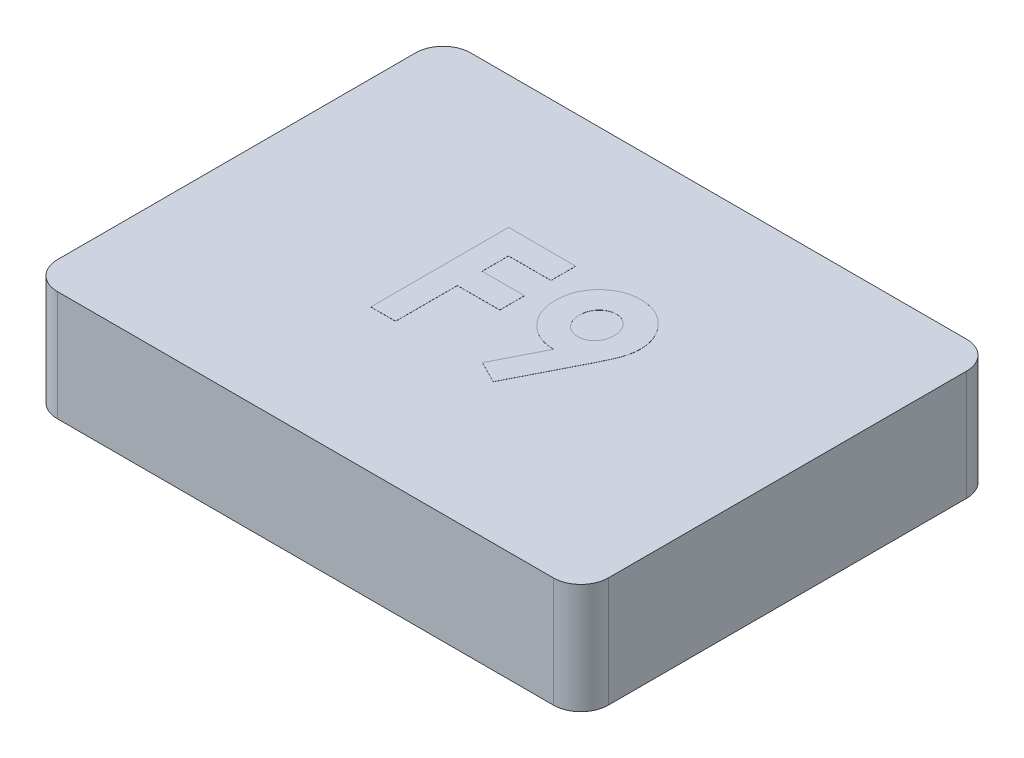
SolidWorks part; units mm, degrees
ref_plane "Front Plane" through (0, 0, 0) normal (0, 0, 1) x (1, 0, 0)
ref_plane "Top Plane" through (0, 0, 0) normal (0, 1, 0) x (1, 0, 0)
ref_plane "Right Plane" through (0, 0, 0) normal (1, 0, 0) x (0, 0, -1)
sketch "Sketch1" plane through (0, 0, 0) normal (0, 1, 0) x (1, 0, 0)
  line L0 (0, 0) -> (12.7, 0)
  line L1 (12.7, 0) -> (12.7, 9.525)
  line L2 (12.7, 9.525) -> (0, 9.525)
  line L3 (0, 9.525) -> (0, 0)
  dimension "D1" = 12.7
  dimension "D2" = 9.525
extrude "Boss-Extrude1" add sketch "Sketch1" along normal blind 2.54
fillet "Fillet1" radius 0.635 4 edges at (0, 1.27, -9.525) (12.7, 1.27, -9.525) (12.7, 1.27, 0) (0, 1.27, 0)
shell "Shell1" thickness 0.635 removed face at (6.35, 0, -4.7625)
sketch "Sketch2" plane through (0, 1.905, 0) normal (0, -1, 0) x (-1, 0, 0)
  line L0 (-0.635, 4.7625) -> (-12.065, 4.7625) construction
  line L1 (-0.635, 8.89) -> (-0.635, 0.635) construction
  line L2 (-12.065, 0.635) -> (-12.065, 8.89) construction
  line L3 (-6.35, 0.635) -> (-6.35, 8.89) construction
  line L4 (-0.635, 0.635) -> (-12.065, 0.635) construction
  line L5 (-12.065, 8.89) -> (-0.635, 8.89) construction
  circle A0 centre (-6.35, 4.7625) radius 2.54
  dimension "D1" = 5.08
extrude "Boss-Extrude2" add sketch "Sketch2" along normal up to surface (1.905 mm away) up to face at (6.35, 0, -4.7625)
sketch "Sketch3" plane through (0, 2.54, 0) normal (0, 1, 0) x (1, 0, 0)
  line L0 (0.635, 0) -> (12.065, 0) construction
  line L1 (0, 8.89) -> (0, 0.635) construction
  text T0 "<b>F9</b>"
  dimension "D1" = 3.302
  dimension "D2" = 4.191
extrude "Boss-Extrude3" add sketch "Sketch3" along normal blind 0.0025
